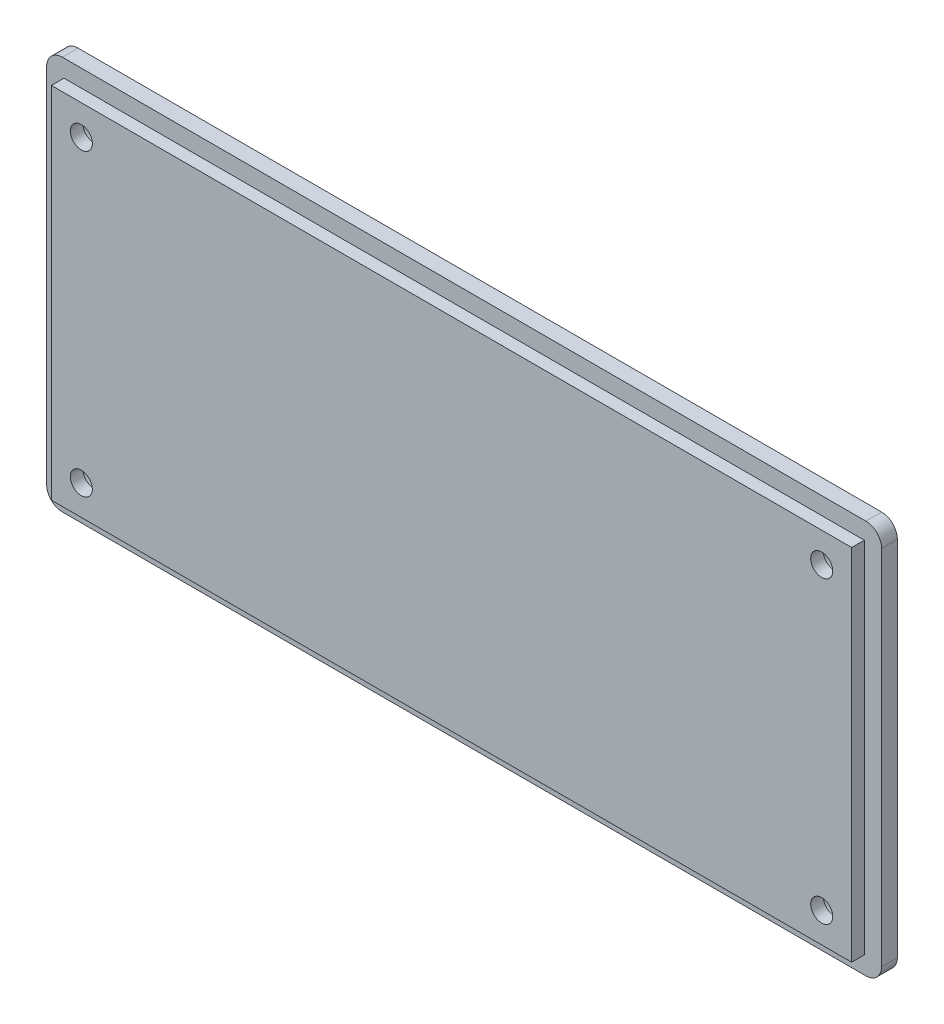
SolidWorks part; units mm, degrees
material "ABS"
ref_plane "Спереди" through (0, 0, 0) normal (0, 0, 1) x (1, 0, 0)
ref_plane "Сверху" through (0, 0, 0) normal (0, 1, 0) x (1, 0, 0)
ref_plane "Справа" through (0, 0, 0) normal (1, 0, 0) x (0, 0, -1)
sketch "Эскиз1" plane through (0, 0, 0) normal (0, 0, 1) x (1, 0, 0)
  line L1 (-53, -25) -> (53, -25)
  line L2 (-53, -25) -> (-53, 25)
  line L3 (-53, 25) -> (53, 25)
  line L4 (53, -25) -> (53, 25)
  line L5 (-53, -25) -> (53, 25) construction
  line L6 (-53, 25) -> (53, -25) construction
  point P0 (0, 0)
  dimension "D1" = 106
  dimension "D2" = 50
extrude "Body" add sketch "Эскиз1" along normal blind 2
sketch "Эскиз2" plane through (0, 0, 2) normal (0, 0, 1) x (1, 0, 0)
  line L0 (-53, 25) -> (-53, -25) construction
  line L1 (-50.8, -22.8) -> (50.8, -22.8)
  line L2 (-50.8, -22.8) -> (-50.8, 22.8)
  line L3 (-50.8, 22.8) -> (50.8, 22.8)
  line L4 (50.8, -22.8) -> (50.8, 22.8)
  line L5 (-50.8, -22.8) -> (50.8, 22.8) construction
  line L6 (-50.8, 22.8) -> (50.8, -22.8) construction
  line L7 (53, 25) -> (-53, 25) construction
  point P0 (0, 0)
  dimension "D1" = 2.2
  dimension "D2" = 2.2
extrude "InternalBody" add sketch "Эскиз2" along normal blind 1.6
sketch "Эскиз3" plane through (0, 0, 0) normal (0, 0, -1) x (-1, 0, 0)
  line L0 (53, -25) -> (-53, -25) construction
  line L1 (51, -23) -> (43, -23) construction
  line L2 (51, -23) -> (51, -15) construction
  line L3 (51, -15) -> (43, -15) construction
  line L4 (43, -23) -> (43, -15) construction
  line L5 (51, -23) -> (43, -15) construction
  line L6 (51, -15) -> (43, -23) construction
  line L7 (53, 25) -> (53, -25) construction
  circle A0 centre (47, -19) radius 1.4
  circle A1 centre (47, -19) radius 2.5
  point P0 (47, -19)
  dimension "D4" = 2.8
  dimension "D5" = 5
  dimension "D1" = 2
  dimension "D2" = 2
  dimension "D3" = 8
extrude "HoleScrew" cut sketch "Эскиз3" against normal through all contours A0 region at (-47, -19, 0)
extrude "TopScrewPlace" cut sketch "Эскиз3<3>" against normal blind 2 contours A1 A0 region at (-44.5707, -19, 0)
sketch "Эскиз3<3>" plane through (0, 0, 0) normal (0, 0, -1) x (-1, 0, 0) same geometry as "Эскиз3"
mirror "ScrewMrror1" about plane through (0, 0, 0) normal (0, 1, 0) of "TopScrewPlace", "HoleScrew"
mirror "ScrewMirror2" about plane through (0, 0, 0) normal (1, 0, 0) of "ScrewMrror1", "TopScrewPlace"
fillet "Corners" radius 2 4 edges at (-53, -25, 1) (53, -25, 1) (53, 25, 1) (-53, 25, 1)
